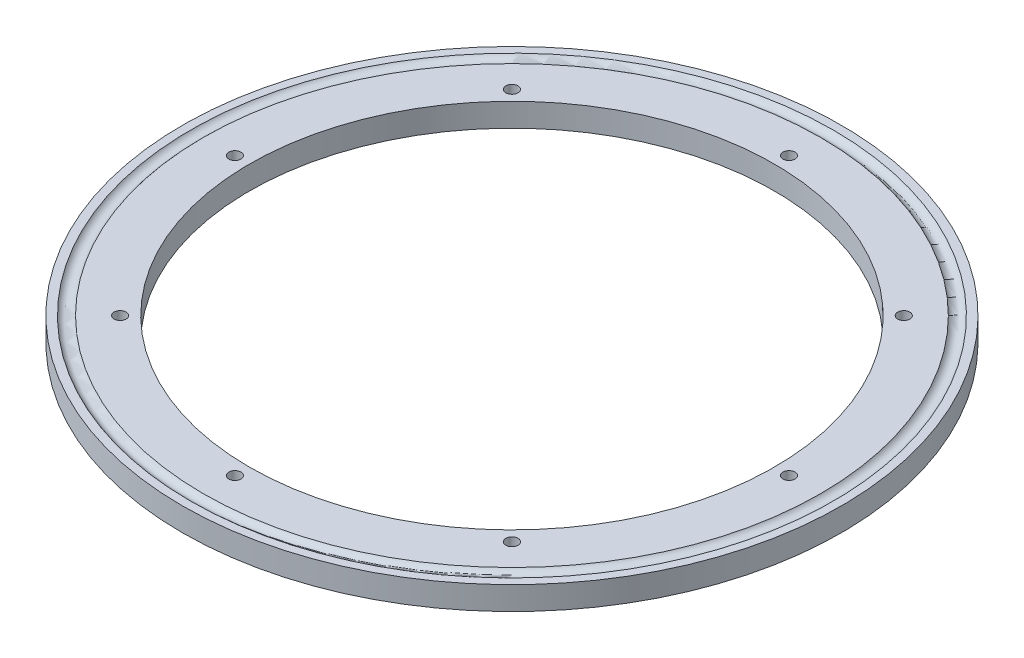
SolidWorks part; units mm, degrees
material "6061 Alloy"
ref_plane "Front Plane" through (0, 0, 0) normal (0, 0, 1) x (1, 0, 0)
ref_plane "Top Plane" through (0, 0, 0) normal (0, 1, 0) x (1, 0, 0)
ref_plane "Right Plane" through (0, 0, 0) normal (1, 0, 0) x (0, 0, -1)
sketch "Sketch1" plane through (0, 0, 0) normal (0, 1, 0) x (1, 0, 0)
  circle A0 centre (0, 0) radius 57.15
  circle A1 centre (0, 0) radius 71.755
  circle A2 centre (0, 0) radius 68.58
  circle A3 centre (0, -60.325) radius 1.3208
  circle A4 centre (-42.6562, -42.6562) radius 1.3208
  circle A5 centre (-60.325, 0) radius 1.3208
  circle A6 centre (-42.6562, 42.6562) radius 1.3208
  circle A7 centre (0, 60.325) radius 1.3208
  circle A8 centre (42.6562, 42.6562) radius 1.3208
  circle A9 centre (60.325, 0) radius 1.3208
  circle A10 centre (42.6562, -42.6562) radius 1.3208
  point P21 (0, 0)
  dimension "D1" = 114.3
  dimension "D4" = 2.6416
  dimension "D5" = 60.325
  dimension "D2" = 14.605
  dimension "D3" = 11.43
  dimension "D6" = 8
extrude "Boss-Extrude1" add sketch "Sketch1" along normal blind 5.08 contours A2 A0 | A1 A2 region at (-69.7255, 0, 0) region at (-66.6403, 0, 0)
sketch "Sketch2" plane through (0, 0, 0) normal (1, 0, 0) x (0, 0, -1)
  line L0 (-71.755, 0) -> (71.755, 0) construction
  line L1 (71.755, 5.08) -> (-71.755, 5.08) construction
  line L2 (-71.755, 0) -> (71.755, 0)
  line L3 (71.755, 5.08) -> (-71.755, 5.08)
  line L4 (89.5975, 4.318) -> (99.9841, 4.318) construction
  line L5 (95.9885, 2.54) -> (99.6739, 2.54) construction
  line L6 (0, 0) -> (0, 18.217) construction
  circle A0 centre (68.58, 5.9055) radius 1.5875 construction
  circle A1 centre (68.58, 5.969) radius 1.651
  circle A2 centre (68.58, -0.889) radius 1.651
  dimension "D3" = 3.175
  dimension "D4" = 3.302
  dimension "D1" = 68.58
  dimension "D2" = 0.762
  dimension "D5" = 2.54
revolve "Cut-Revolve1" cut sketch "Sketch2" angle 360 about L6 region at (0, 0.3118, -68.58) region at (0, 4.7682, -68.58)
equation "\"Middle Coupler Inner Daimeter\"= 4.5in"
equation "\"Middle Coupler  Wall Thickness\" = 0.25in"
equation "\"Middle Coupler Bottom Thickness\"= 0.2in"
equation "\"Bearing Rail Offset\"= 0.45in"
equation "\"3-56 UNF Tap\"= 0.089in"
equation "\"3-56 UNF Clearance\"= 0.104in"
equation "\"D5@Sketch1\"=(\"Middle Coupler Inner Daimeter\"*2+0.5)/4in"
equation "\"Ball Bearing Distance\"= 0.03in"
equation "\"D1@Sketch2\"=\"Middle Coupler Inner Daimeter\"/2+\"Bearing Rail Offset\""
equation "\"D3@Sketch1\"=\"Bearing Rail Offset\""
equation "\"D4@Sketch1\"=\"3-56 UNF Clearance\""
equation "\"D1@Sketch1\"=\"Middle Coupler Inner Daimeter\""
equation "\"D2@Sketch2\"=\"Ball Bearing Distance\""
equation "\"D4@Sketch2\"=\"D3@Sketch2\"+0.005"
equation "\"D5@Sketch2\"=\"Middle Coupler Bottom Thickness\"/2"
equation "\"TCA Outer Diameter\" = 6.625in"
equation "\"Interstage Aeroframe Wall Thickness\" = 0.072in"
equation "\"Compression Spring OD\"= 0.42in"
equation "\"10-24 Tap\"= 0.157in"
equation "\"10-24 Clearance\"= 0.196in"
equation "\"Lower Stage Fuselage Wall Thickness\" = 0.25in"
equation "\"6-32 Tap\" = 0.107in"
equation "\"1/4-20 Tap\" = 0.201in"
